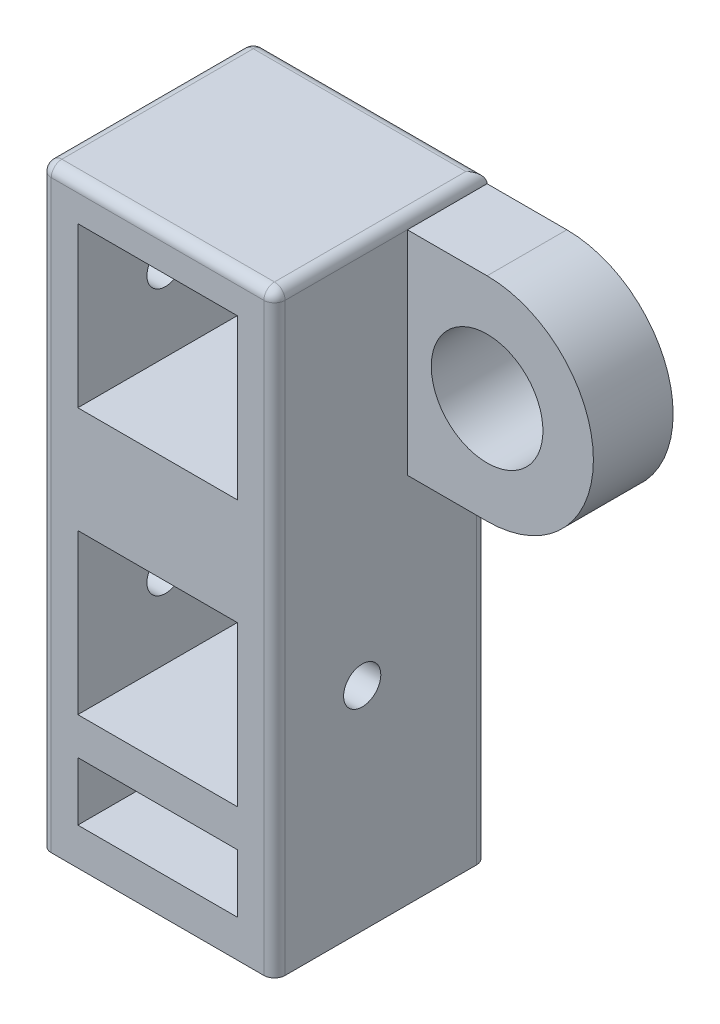
SolidWorks part; units mm, degrees
ref_plane "Front Plane" through (0, 0, 0) normal (0, 0, 1) x (1, 0, 0)
ref_plane "Top Plane" through (0, 0, 0) normal (0, 1, 0) x (1, 0, 0)
ref_plane "Right Plane" through (0, 0, 0) normal (1, 0, 0) x (0, 0, -1)
sketch "Sketch1" plane through (0, 0, 0) normal (0, 0, 1) x (1, 0, 0)
  line L1 (-25.0962, 42.3339) -> (-3.0962, 42.3339)
  line L2 (-25.0962, 42.3339) -> (-25.0962, -13.6661)
  line L3 (-25.0962, -13.6661) -> (-3.0962, -13.6661)
  line L4 (-3.0962, 42.3339) -> (-3.0962, -13.6661)
  line L5 (-21.5962, 38.8339) -> (-6.5962, 38.8339)
  line L6 (-21.5962, 38.8339) -> (-21.5962, 23.8339)
  line L7 (-21.5962, 23.8339) -> (-6.5962, 23.8339)
  line L8 (-6.5962, 38.8339) -> (-6.5962, 23.8339)
  dimension "D1" = 22
  dimension "D2" = 56
  dimension "D3" = 15
  dimension "D4" = 3.5
  dimension "D5" = 3.5
  dimension "D6" = 15
extrude "Boss-Extrude1" add sketch "Sketch1" along normal blind 20
sketch "Sketch2" plane through (0, 0, 20) normal (0, 0, 1) x (1, 0, 0)
  line L0 (-3.0962, -13.6661) -> (-3.0962, 42.3339) construction
  line L1 (-21.5962, 13.8339) -> (-6.5962, 13.8339)
  line L2 (-21.5962, 13.8339) -> (-21.5962, -1.1661)
  line L3 (-21.5962, -1.1661) -> (-6.5962, -1.1661)
  line L4 (-6.5962, 13.8339) -> (-6.5962, -1.1661)
  line L5 (-21.5962, 23.8339) -> (-6.5962, 23.8339) construction
  line L6 (-25.0962, -13.6661) -> (-3.0962, -13.6661) construction
  line L7 (-21.5962, -4.6661) -> (-6.5962, -4.6661)
  line L8 (-21.5962, -4.6661) -> (-21.5962, -10.1661)
  line L9 (-21.5962, -10.1661) -> (-6.5962, -10.1661)
  line L10 (-6.5962, -4.6661) -> (-6.5962, -10.1661)
  dimension "D1" = 15
  dimension "D2" = 3.5
  dimension "D3" = 10
  dimension "D4" = 15
  dimension "D5" = 15
  dimension "D6" = 3.5
  dimension "D7" = 3.5
extrude "Cut-Extrude1" cut sketch "Sketch2" against normal offset from surface (15.5 mm away) 4.5 up to face at (-14.0962, 14.3339, 0)
sketch "Sketch4" plane through (0, 0, 0) normal (0, 0, -1) x (-1, 0, 0)
  line L0 (6.5962, 31.3339) -> (-21.8805, 31.3339) construction
  line L2 (6.5962, 23.8339) -> (6.5962, 38.8339) construction
  line L5 (3.0962, -13.6661) -> (3.0962, 42.3339) construction
  line L6 (-4.4038, 41.3339) -> (3.0962, 41.3339)
  line L7 (3.0962, 41.3339) -> (3.0962, 21.3339)
  line L8 (3.0962, 21.3339) -> (-4.4038, 21.3339)
  circle A0 centre (-4.4038, 31.3339) radius 5.25
  arc A1 (-4.4038, 41.3339) -> (-4.4038, 21.3339) centre (-4.4038, 31.3339) ccw
  dimension "D1" = 20
  dimension "D2" = 10.5
  dimension "D3" = 7.5
extrude "Boss-Extrude3" add sketch "Sketch4" against normal blind 7.5
fillet "Fillet4" radius 1 8 edges at (-3.0962, 14.3339, 20) (-25.0962, 14.3339, 0) (-25.0962, 14.3339, 20) (-14.0962, 42.3339, 20) (-3.0962, 42.3339, 10) (-14.0962, 42.3339, 0) (-25.0962, 42.3339, 10)
sketch "Sketch6" plane through (-25.0962, 0, 0) normal (-1, 0, 0) x (0, 0, 1)
  line L0 (11.75, -13.6661) -> (11.75, 44.2765) construction
  line L1 (19, -13.6661) -> (1, -13.6661) construction
  line L2 (20, 41.3339) -> (20, -13.6661) construction
  line L3 (20, 38.8339) -> (0, 38.8339) construction
  line L4 (4.5, 13.8339) -> (20, 13.8339) construction
  circle A0 centre (11.75, 31.3339) radius 1.75
  circle A1 centre (11.75, 6.3339) radius 1.75
  dimension "D2" = 3.5
  dimension "D3" = 7.5
  dimension "D4" = 7.5
  dimension "D1" = 8.25
extrude "Cut-Extrude2" cut sketch "Sketch6" against normal blind 10
sketch "Sketch7" plane through (-3.0962, 0, 0) normal (1, 0, 0) x (0, 0, -1)
  circle A0 centre (-11.75, 6.3339) radius 1.75
extrude "Cut-Extrude3" cut sketch "Sketch7" against normal blind 10
